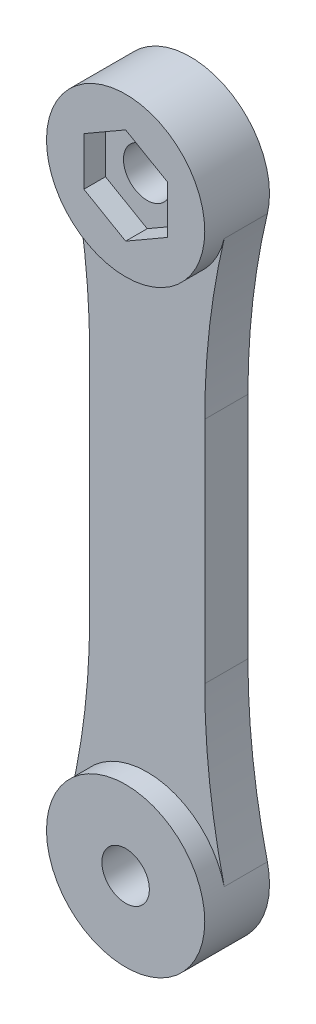
SolidWorks part; units mm, degrees
ref_plane "Front Plane" through (0, 0, 0) normal (0, 0, 1) x (1, 0, 0)
ref_plane "Top Plane" through (0, 0, 0) normal (0, 1, 0) x (1, 0, 0)
ref_plane "Right Plane" through (0, 0, 0) normal (1, 0, 0) x (0, 0, -1)
sketch "草图1" plane through (0, 0, 0) normal (0, 0, 1) x (1, 0, 0)
  line L0 (-6.2763, 0.3095) -> (16.1865, 0.3095) construction
  line L2 (-2.1704, 17.3095) -> (-2.1704, -16.6905)
  line L4 (5.8296, 17.3095) -> (5.8296, -16.6905)
  arc A0 (5.8296, -16.6905) -> (-2.1704, -16.6905) centre (1.8296, -20.4654) cw
  arc A3 (5.8296, 17.3095) -> (-2.1704, 17.3095) centre (1.8296, 21.0844) ccw
  circle A4 centre (1.8296, 21.0844) radius 1.65
  circle A5 centre (1.8296, -20.4654) radius 1.65
  point P3 (-2.1704, 0.3095)
  point P12 (5.8296, 0.3095)
  dimension "D5" = 3.3
  dimension "D6" = 5.5
  dimension "D4" = 3.3
  dimension "D1" = 17
  dimension "D2" = 4
  dimension "D3" = 8
extrude "凸台-拉伸1" add sketch "草图1" along normal blind 3
sketch "草图2" plane through (0, 0, 3) normal (0, 0, 1) x (1, 0, 0)
  line L0 (-1.0704, 22.7587) -> (-1.0704, 19.4101)
  line L1 (4.7296, 22.7587) -> (4.7296, 19.4101)
  line L2 (-1.0704, 22.7587) -> (1.8296, 24.4331)
  line L3 (1.8296, 24.4331) -> (4.7296, 22.7587)
  line L4 (-1.0704, 19.4101) -> (1.8296, 17.7358)
  line L5 (1.8296, 17.7358) -> (4.7296, 19.4101)
  line L6 (1.8296, 24.4331) -> (1.8296, 17.7358) construction
  line L7 (-1.0704, 19.4101) -> (4.7296, 22.7587) construction
  circle A0 centre (1.8296, 21.0844) radius 5.5
  circle A1 centre (1.8296, -20.4654) radius 5.5
  arc A2 (-2.1704, -16.6905) -> (5.8296, -16.6905) centre (1.8296, -20.4654) ccw construction
  circle A3 centre (1.8296, -20.4654) radius 1.65
  point P4 (1.8296, 21.0844)
  point P11 (1.8296, -20.4654)
  dimension "D1" = 5.8
  dimension "D2" = 60
  dimension "D3" = 120
extrude "凸台-拉伸2" add sketch "草图2" along normal blind 1.5
fillet "圆角2" radius 50 4 edges at (-2.1704, -16.6905, 1.5) (5.8296, -16.6905, 1.5) (-2.1704, 17.3095, 1.5) (5.8296, 17.3095, 1.5)
sketch "草图5" plane through (0, 0, 0) normal (0, 0, -1) x (-1, 0, 0)
  line L0 (-4.7296, -18.7911) -> (-4.7296, -22.1397)
  line L1 (1.0704, -18.7911) -> (1.0704, -22.1397)
  line L2 (-4.7296, -18.7911) -> (-1.8296, -17.1168)
  line L3 (-1.8296, -17.1168) -> (1.0704, -18.7911)
  line L4 (-4.7296, -22.1397) -> (-1.8296, -23.814)
  line L5 (-1.8296, -23.814) -> (1.0704, -22.1397)
  line L6 (-1.8296, -17.1168) -> (-1.8296, -23.814) construction
  line L7 (-4.7296, -22.1397) -> (1.0704, -18.7911) construction
  point P4 (-1.8296, -20.4654)
  dimension "D1" = 120
  dimension "D2" = 5.8
extrude "切除-拉伸1" cut sketch "草图5" against normal blind 1.5
